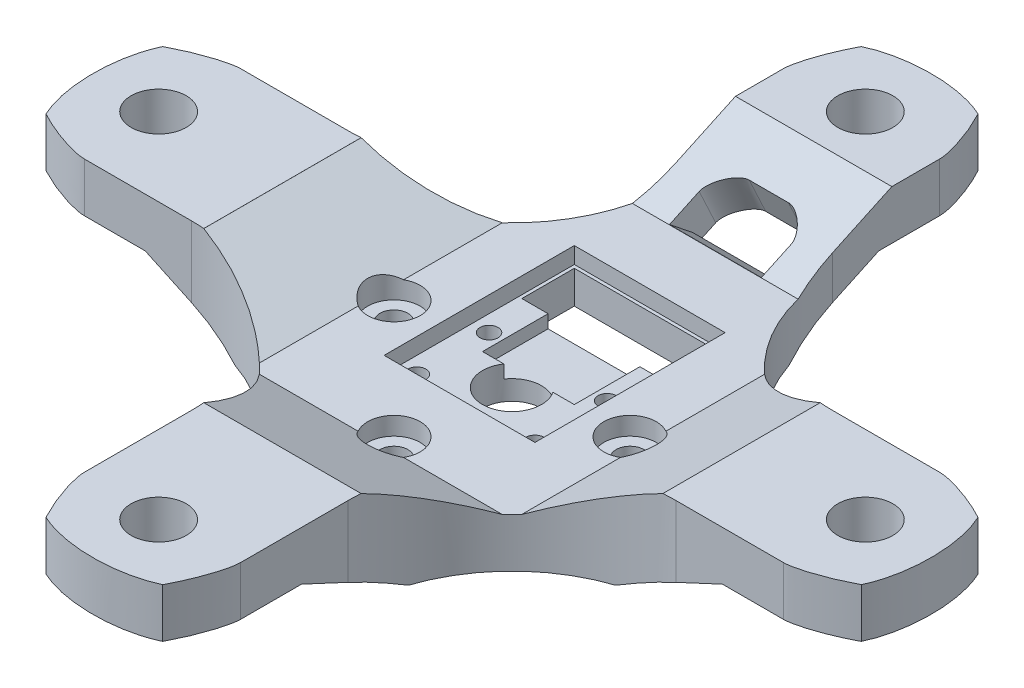
SolidWorks part; units mm, degrees
ref_plane "Front Plane" through (0, 0, 0) normal (0, 0, 1) x (1, 0, 0)
ref_plane "Top Plane" through (0, 0, 0) normal (0, 1, 0) x (1, 0, 0)
ref_plane "Right Plane" through (0, 0, 0) normal (1, 0, 0) x (0, 0, -1)
other "Bounding Box"
ref_plane "Default Plane" through (0, 0, 71.0595) normal (-0.7071, 0, -0.7071) x (-0.7071, 0, 0.7071)
sketch "Sketch1" plane through (0, 0, 0) normal (0, 1, 0) x (1, 0, 0)
  line L0 (0, -1000) -> (0, 49000) construction
  line L7 (0, 71.842) -> (71.842, 0)
  line L8 (0, 71.842) -> (-71.842, 0)
  line L9 (-71.842, 0) -> (0, -71.842)
  line L10 (71.842, 0) -> (0, -71.842)
  line L11 (0, 71.842) -> (0, -71.842) construction
  line L12 (-71.842, 0) -> (71.842, 0) construction
  dimension "D1" = 101.6
  dimension "D2" = 101.6
  dimension "D6" = 90
extrude "Base Plate" add sketch "Sketch1" along normal blind 7.5
sketch "Hole Pattern" plane through (0, 0, 0) normal (0, -1, 0) x (1, 0, 0)
  line L0 (-1000, 0) -> (49000, 0) construction
  line L1 (0, 0) -> (-48, 0) construction
  line L2 (0, 0) -> (0, 18) construction
  line L3 (0, 0) -> (18, 0) construction
  circle A0 centre (0, 0) radius 48 construction
  circle A7 centre (0, 0) radius 18 construction
  circle A8 centre (0, 18) radius 2.125
  circle A9 centre (18, 0) radius 2.125
  circle A10 centre (0, -18) radius 2.125 [skipped]
  circle A11 centre (-18, 0) radius 2.125
  dimension "D1" = 96
  dimension "D6" = 36
  dimension "D7" = 4.25
  dimension "D11" = 18
  dimension "D3" = 0
  dimension "D9" = 90
  dimension "D10" = 18
  dimension "D8" = 4
extrude "Motor Mount Holes" cut sketch "Hole Pattern" against normal through all
sketch "Sketch3" plane through (0, 7.5, 0) normal (0, 1, 0) x (1, 0, 0)
  line L1 (-9, -5.5) -> (9, -5.5) construction
  line L2 (-9, -5.5) -> (-9, 5.5) construction
  line L3 (-9, 5.5) -> (9, 5.5) construction
  line L4 (9, -5.5) -> (9, 5.5) construction
  line L5 (-9, -5.5) -> (9, 5.5) construction
  line L6 (-9, 5.5) -> (9, -5.5) construction
  circle A0 centre (-9, 5.5) radius 1.375
  circle A1 centre (9, 5.5) radius 1.375
  circle A2 centre (9, -5.5) radius 1.375
  circle A3 centre (-9, -5.5) radius 1.375
  circle A4 centre (0, 0) radius 4.5
  point P0 (0, 0)
  dimension "D3" = 2.75
  dimension "D4" = 9
  dimension "D1" = 11
  dimension "D2" = 18
extrude "Encoder mounting holes" cut sketch "Sketch3" against normal through all
sketch "Sketch4" plane through (0, 0, 0) normal (0, 1, 0) x (1, 0, 0)
  line L1 (-9, -5.5) -> (9, -5.5) construction
  line L2 (-9, -5.5) -> (-9, 5.5) construction
  line L3 (-9, 5.5) -> (9, 5.5) construction
  line L4 (9, -5.5) -> (9, 5.5) construction
  line L5 (-9, -5.5) -> (9, 5.5) construction
  line L6 (-9, 5.5) -> (9, -5.5) construction
  line L7 (-11, -7.5) -> (11, -7.5) construction
  line L8 (-11, -7.5) -> (-11, 20.5) construction
  line L9 (-11, 20.5) -> (11, 20.5) construction
  line L10 (11, -7.5) -> (11, 20.5) construction
  line L11 (-11, 20.5) -> (11, 20.5)
  line L12 (-11, 20.5) -> (-11, 12.5)
  line L13 (-11, 12.5) -> (11, 12.5)
  line L14 (11, 20.5) -> (11, 12.5)
  point P0 (0, 0)
  dimension "D1" = 22
  dimension "D2" = 28
  dimension "D3" = 2
  dimension "D4" = 2
  dimension "D5" = 8
extrude "Encoder Wire Pass through" cut sketch "Sketch4" along normal blind 5
sketch "Motor Wire Pass thru plane sketch" plane through (0, 0, 0) normal (0, 1, 0) x (1, 0, 0)
  line L0 (0, 0) -> (-22.6274, 22.6274) construction
  line L1 (-31.3955, 21.8496) -> (-27.4004, 17.8544)
  line L2 (-31.3955, 21.8496) -> (-21.8496, 31.3955)
  line L3 (-27.4004, 17.8544) -> (-17.8544, 27.4004)
  line L4 (-21.8496, 31.3955) -> (-17.8544, 27.4004)
  line L5 (-31.3955, 21.8496) -> (-17.8544, 27.4004) construction
  line L6 (-27.4004, 17.8544) -> (-21.8496, 31.3955) construction
  line L8 (-1000, 0) -> (49000, 0) construction
  point P4 (-24.625, 24.625)
  point P10 (-22.6274, 22.6274)
  dimension "D1" = 13.5
  dimension "D2" = 5.65
  dimension "D3" = 32
  dimension "D4" = 45
  dimension "D5" = 90
sketch "Sketch7" plane through (0, 0, 0) normal (0, -1, 0) x (1, 0, 0)
  line L1 (7.5566, 3) -> (10.4434, 3)
  line L2 (10.4434, 3) -> (11.8868, 5.5)
  line L3 (11.8868, 5.5) -> (10.4434, 8)
  line L4 (10.4434, 8) -> (7.5566, 8)
  line L5 (7.5566, 8) -> (6.1132, 5.5)
  line L6 (6.1132, 5.5) -> (7.5566, 3)
  line L7 (10.4434, -8) -> (11.8868, -5.5)
  line L8 (11.8868, -5.5) -> (10.4434, -3)
  line L9 (10.4434, -3) -> (7.5566, -3)
  line L10 (7.5566, -3) -> (6.1132, -5.5)
  line L11 (6.1132, -5.5) -> (7.5566, -8)
  line L12 (7.5566, -8) -> (10.4434, -8)
  line L13 (-7.5566, -8) -> (-6.1132, -5.5)
  line L14 (-6.1132, -5.5) -> (-7.5566, -3)
  line L15 (-7.5566, -3) -> (-10.4434, -3)
  line L16 (-10.4434, -3) -> (-11.8868, -5.5)
  line L17 (-11.8868, -5.5) -> (-10.4434, -8)
  line L18 (-10.4434, -8) -> (-7.5566, -8)
  line L19 (-7.5566, 3) -> (-6.1132, 5.5)
  line L20 (-6.1132, 5.5) -> (-7.5566, 8)
  line L21 (-7.5566, 8) -> (-10.4434, 8)
  line L22 (-10.4434, 8) -> (-11.8868, 5.5)
  line L23 (-11.8868, 5.5) -> (-10.4434, 3)
  line L24 (-10.4434, 3) -> (-7.5566, 3)
  circle A0 centre (9, 5.5) radius 2.5 construction
  circle A1 centre (9, -5.5) radius 2.5 construction
  circle A2 centre (-9, -5.5) radius 2.5 construction
  circle A3 centre (-9, 5.5) radius 2.5 construction
  point P1 (6.8349, 6.75)
  dimension "D1" = 5
extrude "Cut-Extrude7" cut sketch "Sketch7" against normal blind 2
sketch "Sketch10" plane through (0, 7.5, 0) normal (0, 1, 0) x (1, 0, 0)
  line L1 (-11.5, 21) -> (11.5, 21)
  line L2 (-11.5, 21) -> (-11.5, -8)
  line L3 (-11.5, -8) -> (11.5, -8)
  line L4 (11.5, 21) -> (11.5, -8)
  circle A0 centre (0, 0) radius 4.5 construction
  dimension "D1" = 23
  dimension "D2" = 29
  dimension "D3" = 8
  dimension "D4" = 11.5
extrude "Cut-Extrude9" cut sketch "Sketch10" against normal blind 2.5
sketch "Sketch11" plane through (0, 7.5, 0) normal (0, 1, 0) x (1, 0, 0)
  circle A0 centre (18, 0) radius 4
  circle A1 centre (0, -18) radius 4
  circle A2 centre (-18, 0) radius 4
  circle A3 centre (0, 18) radius 4 [skipped]
  dimension "D1" = 8
  dimension "D2" = 4
extrude "Cut-Extrude10" cut sketch "Sketch11" against normal blind 2.75
sketch "Sketch14" plane through (0, 0, 0) normal (0, -1, 0) x (1, 0, 0)
  line L0 (-53.8815, 0) -> (0, -53.8815) construction
  line L1 (-53.8815, 0) -> (0, 53.8815) construction
  line L2 (0, -53.8815) -> (53.8815, 0) construction
  line L3 (0, 53.8815) -> (53.8815, 0) construction
  line L4 (-53.8815, 0) -> (53.8815, 0) construction
  line L5 (0, -53.8815) -> (0, 53.8815) construction
  line L6 (0, 71.842) -> (71.842, 0) construction
  circle A0 centre (0, 0) radius 43.55 construction
  dimension "D1" = 87.1
  dimension "D2" = 76.2
  dimension "D3" = 76.2
sketch "Sketch18" plane through (0, 0, 0) normal (0, -1, 0) x (1, 0, 0)
  line L0 (0, -71.842) -> (-71.842, 0) construction
  line L1 (-59.921, -59.921) -> (-11.921, -59.921)
  line L2 (-59.921, -59.921) -> (-59.921, -11.921)
  line L3 (-59.921, -11.921) -> (-11.921, -11.921)
  line L4 (-11.921, -59.921) -> (-11.921, -11.921)
  line L5 (-59.921, -59.921) -> (-11.921, -11.921) construction
  line L6 (-59.921, -11.921) -> (-11.921, -59.921) construction
  line L19 (-59.921, 59.921) -> (-11.921, 59.921)
  line L20 (-59.921, 59.921) -> (-59.921, 11.921)
  line L21 (-59.921, 11.921) -> (-11.921, 11.921)
  line L22 (-11.921, 59.921) -> (-11.921, 11.921)
  line L23 (59.921, 59.921) -> (59.921, 11.921)
  line L24 (59.921, 59.921) -> (11.921, 59.921)
  line L25 (11.921, 59.921) -> (11.921, 11.921)
  line L26 (59.921, 11.921) -> (11.921, 11.921)
  line L27 (59.921, -59.921) -> (11.921, -59.921)
  line L28 (59.921, -59.921) -> (59.921, -11.921)
  line L29 (59.921, -11.921) -> (11.921, -11.921)
  line L30 (11.921, -59.921) -> (11.921, -11.921)
  point P0 (-35.921, -35.921)
  dimension "D1" = 48
  dimension "D2" = 4
extrude "Cut-Extrude12" cut sketch "Sketch18" against normal through all
sketch "Sketch25" plane through (0, 7.5, 0) normal (0, 1, 0) x (1, 0, 0)
  line L0 (-11.921, 35) -> (11.921, 35)
  line L1 (-11.921, 35) -> (-11.921, 59.921)
  line L2 (11.921, 35) -> (11.921, 59.921)
  line L4 (-11.921, 59.921) -> (-11.921, 11.921) construction
  line L5 (11.921, 11.921) -> (11.921, 59.921) construction
  line L18 (11.921, 59.921) -> (0, 71.842)
  line L19 (0, 71.842) -> (-11.921, 59.921)
  line L50 (35, 11.921) -> (35, -11.921)
  line L51 (35, 11.921) -> (59.921, 11.921)
  line L52 (35, -11.921) -> (59.921, -11.921)
  line L53 (59.921, -11.921) -> (71.842, 0)
  line L54 (71.842, 0) -> (59.921, 11.921)
  line L55 (11.921, -35) -> (-11.921, -35)
  line L56 (11.921, -35) -> (11.921, -59.921)
  line L57 (-11.921, -35) -> (-11.921, -59.921)
  line L58 (-11.921, -59.921) -> (0, -71.842)
  line L59 (0, -71.842) -> (11.921, -59.921)
  line L60 (-35, -11.921) -> (-35, 11.921)
  line L61 (-35, -11.921) -> (-59.921, -11.921)
  line L62 (-35, 11.921) -> (-59.921, 11.921)
  line L63 (-59.921, 11.921) -> (-71.842, 0)
  line L64 (-71.842, 0) -> (-59.921, -11.921)
  dimension "D1" = 35
  dimension "D2" = 4
extrude "Boss-Extrude3" add sketch "Sketch25" along normal blind 7
sketch "Sketch26" plane through (0, 0, 0) normal (0, -1, 0) x (1, 0, 0)
  line L0 (-11.921, 44) -> (11.921, 44)
  line L1 (-11.921, 11.921) -> (-11.921, 59.921) construction
  line L2 (11.921, 59.921) -> (11.921, 11.921) construction
  line L3 (11.921, 44) -> (11.921, 59.921)
  line L4 (11.921, 59.921) -> (0, 71.842)
  line L5 (0, 71.842) -> (-11.921, 59.921)
  line L6 (-11.921, 59.921) -> (-11.921, 44)
  line L37 (44, 11.921) -> (44, -11.921)
  line L38 (44, -11.921) -> (59.921, -11.921)
  line L39 (59.921, -11.921) -> (71.842, 0)
  line L40 (71.842, 0) -> (59.921, 11.921)
  line L41 (59.921, 11.921) -> (44, 11.921)
  line L42 (11.921, -44) -> (-11.921, -44)
  line L43 (-11.921, -44) -> (-11.921, -59.921)
  line L44 (-11.921, -59.921) -> (0, -71.842)
  line L45 (0, -71.842) -> (11.921, -59.921)
  line L46 (11.921, -59.921) -> (11.921, -44)
  line L47 (-44, -11.921) -> (-44, 11.921)
  line L48 (-44, 11.921) -> (-59.921, 11.921)
  line L49 (-59.921, 11.921) -> (-71.842, 0)
  line L50 (-71.842, 0) -> (-59.921, -11.921)
  line L51 (-59.921, -11.921) -> (-44, -11.921)
extrude "Cut-Extrude16" cut sketch "Sketch26" against normal blind 7
hole_wizard "M8 Clearance Hole1" positions "Sketch16" profile "Sketch17" hole size "M8" standard "ANSI Metric" end condition through all
sketch "Sketch16" plane through (0, 0, 0) normal (0, -1, 0) x (-1, 0, 0)
  point P0 (53.8815, 0)
  point P3 (0, -53.8815)
  point P6 (-53.8815, 0)
  point P9 (0, 53.8815)
sketch "Sketch17" plane through (-53.8815, 0, 0) normal (1, 0, 0) x (0, 0, -1)
  line L0 (0, 0) -> (0, 14.5)
  line L1 (0, 14.5) -> (4.2, 14.5)
  line L2 (4.2, 14.5) -> (4.2, 0)
  line L5 (4.2, 0) -> (0, 0)
  line L11 (0, -6.35) -> (0, 107.95) construction
  dimension "Thru Hole Dia." = 8.4
  dimension "Thru Hole Depth" = 14.5
fillet "Fillet2" radius 25 4 edges at (11.921, 3.75, -11.921) (11.921, 3.75, 11.921) (-11.921, 3.75, 11.921) (-11.921, 3.75, -11.921)
sketch "Sketch22" plane through (0, 5, 0) normal (0, 1, 0) x (1, 0, 0)
  line L0 (-11, 12.5) -> (11, 12.5) construction
  line L1 (-7, 12.5) -> (7, 12.5)
  line L2 (-7, 12.5) -> (-7, 2.5)
  line L3 (-7, 2.5) -> (7, 2.5)
  line L4 (7, 12.5) -> (7, 2.5)
  line L5 (0, -1000) -> (0, 49000) construction
  point P7 (0, 12.5)
  dimension "D1" = 14
  dimension "D2" = 10
extrude "Cut-Extrude13" cut sketch "Sketch22" against normal blind 2
fillet "Fillet7" radius 16 12 edges at (11.921, 10.75, -59.921) (0, 10.75, -71.842) (-11.921, 10.75, -59.921) (-59.921, 10.75, -11.921) (-71.842, 10.75, 0) (-59.921, 10.75, 11.921) (-11.921, 10.75, 59.921) (0, 10.75, 71.842) (11.921, 10.75, 59.921) (59.921, 10.75, -11.921) (59.921, 10.75, 11.921) (71.842, 10.75, 0) conic rho 0.3
chamfer "Chamfer1" distance 15 angle 25 4 edges at (44, 0, 0) (0, 0, -44) (-44, 0, 0) (0, 0, 44) first distance on face at (-9, 0, 5.5)
chamfer "Chamfer2" distance 15 angle 25 3 edges at (-35, 7.5, 0) (0, 7.5, 35) (35, 7.5, 0) first distance on face at (18, 7.5, 4)
sketch "Sketch28" plane through (0, 14.5, 0) normal (0, 1, 0) x (1, 0, 0)
  line L0 (-11.9949, 35) -> (11.9949, 35)
  line L1 (-11.9949, 35) -> (-11.9949, 46)
  line L2 (11.9949, 35) -> (11.9949, 46)
  line L3 (-11.9949, 46) -> (11.9949, 46)
  dimension "D1" = 11
extrude "Cut-Extrude18" cut sketch "Sketch28" against normal blind 7
chamfer "Chamfer5" distance 7 angle 65 1 edges at (0, 7.5, -46) first distance on face at (0, 11, -46)
sketch "Sketch30" plane through (0, -11.1076, -5.1796) normal (0, -0.9063, -0.4226) x (1, 0, 0)
  line L0 (0, -1042.8336) -> (0, 48957.1664) construction
  line L1 (7, -40.2829) -> (-7, -40.2829)
  line L2 (7, -40.2829) -> (7, -33.2829)
  line L3 (7, -33.2829) -> (-7, -33.2829)
  line L4 (-7, -40.2829) -> (-7, -33.2829)
  line L5 (11.921, -42.8336) -> (-11.921, -42.8336) construction
  line L6 (-13.2091, -26.2829) -> (13.2091, -26.2829) construction
  point P5 (0, -40.2829)
  point P9 (0, -42.8336)
  dimension "D1" = 7
  dimension "D2" = 7
  dimension "D3" = 14
extrude "Cut-Extrude19" cut sketch "Sketch30" against normal blind 7
chamfer "Chamfer6" distance 4 distance2 2 1 edges at (0, 8.3572, -32.8266) first distance on face at (0, 5.6577, -34.0854)
fillet "Fillet8" radius 4 2 edges at (7, 8.6161, -40.4296) (-7, 8.6161, -40.4296) conic rho 0.3
equation "\"encoderCutout\"=2.5"
equation "\"D1@Cut-Extrude9\"=\"encoderCutout\""
equation "\"encoderAirGap\"=5"
equation "\"D1@Encoder Wire Pass through\"=\"encoderAirGap\""
equation "\"D1@Base Plate\"=\"encoderCutout\"+\"encoderAirGap\""
